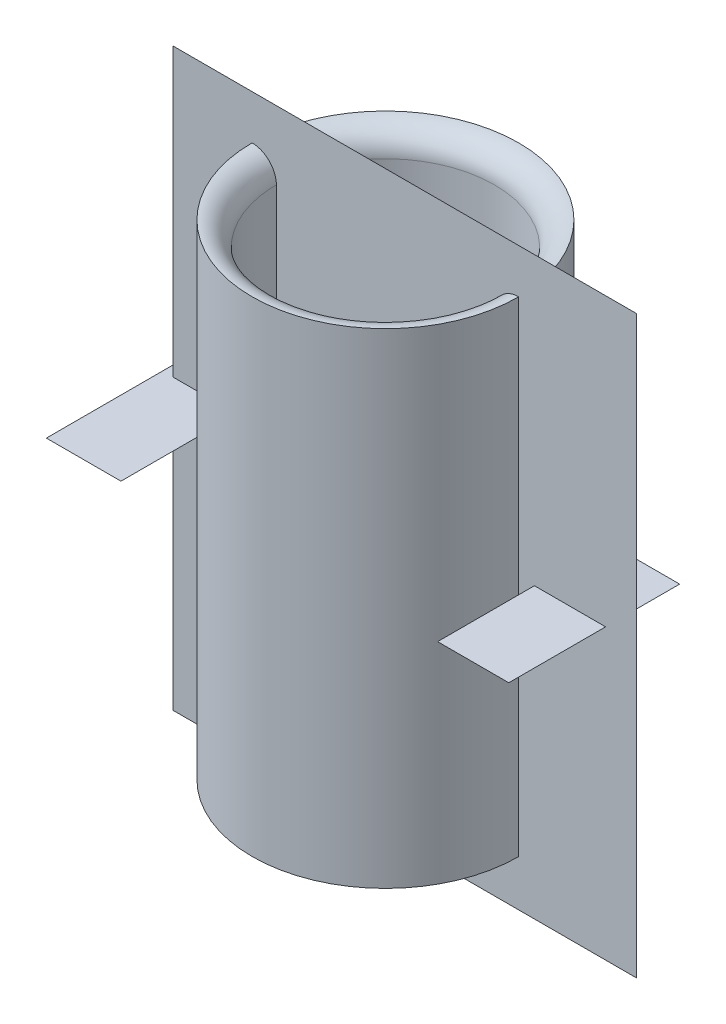
SolidWorks part; units mm, degrees
ref_plane "Спереди" through (0, 0, 0) normal (0, 0, 1) x (1, 0, 0)
ref_plane "Сверху" through (0, 0, 0) normal (0, 1, 0) x (1, 0, 0)
ref_plane "Справа" through (0, 0, 0) normal (1, 0, 0) x (0, 0, -1)
sketch "Эскиз1" plane through (0, 0, 0) normal (0, 0, 1) x (1, 0, 0)
  line L0 (0, -110.6031) -> (0, 130.0787) construction
  line L1 (45, 100) -> (55, 100)
  line L2 (45, 100) -> (45, -100)
  line L3 (45, -100) -> (55, -100)
  line L4 (55, 100) -> (55, -100)
  point P4 (45, 0)
  dimension "D1" = 10
  dimension "D2" = 200
  dimension "D3" = 45
revolve "Повернуть1" add sketch "Эскиз1" angle 360 about L0
sketch "Эскиз2_fr" plane through (0, 0, 0) normal (0, 0, 1) x (1, 0, 0)
  line L1 (-87.5897, 118.3128) -> (103.6191, 118.3128)
  line L2 (-87.5897, 118.3128) -> (-87.5897, -119.0761)
  line L3 (-87.5897, -119.0761) -> (103.6191, -119.0761)
  line L4 (103.6191, 118.3128) -> (103.6191, -119.0761)
surface "Поверхность-Заполнить1" sketch "Эскиз2_fr"
sketch "Эскиз3" plane through (0, 0, 0) normal (0, 1, 0) x (1, 0, 0)
  line L1 (61.468, 30.5447) -> (90.838, 30.5447)
  line L2 (61.468, 30.5447) -> (61.468, -39.9431)
  line L3 (61.468, -39.9431) -> (90.838, -39.9431)
  line L4 (90.838, 30.5447) -> (90.838, -39.9431)
  line L5 (-91.9605, 36.6537) -> (-61.1808, 36.6537)
  line L6 (-91.9605, 36.6537) -> (-91.9605, -47.9317)
  line L7 (-91.9605, -47.9317) -> (-61.1808, -47.9317)
  line L8 (-61.1808, 36.6537) -> (-61.1808, -47.9317)
surface "Поверхность-Плоскость2" sketch "Эскиз3"
fillet "Скругление2" radius 10 1 edges at (0, 100, -45)
